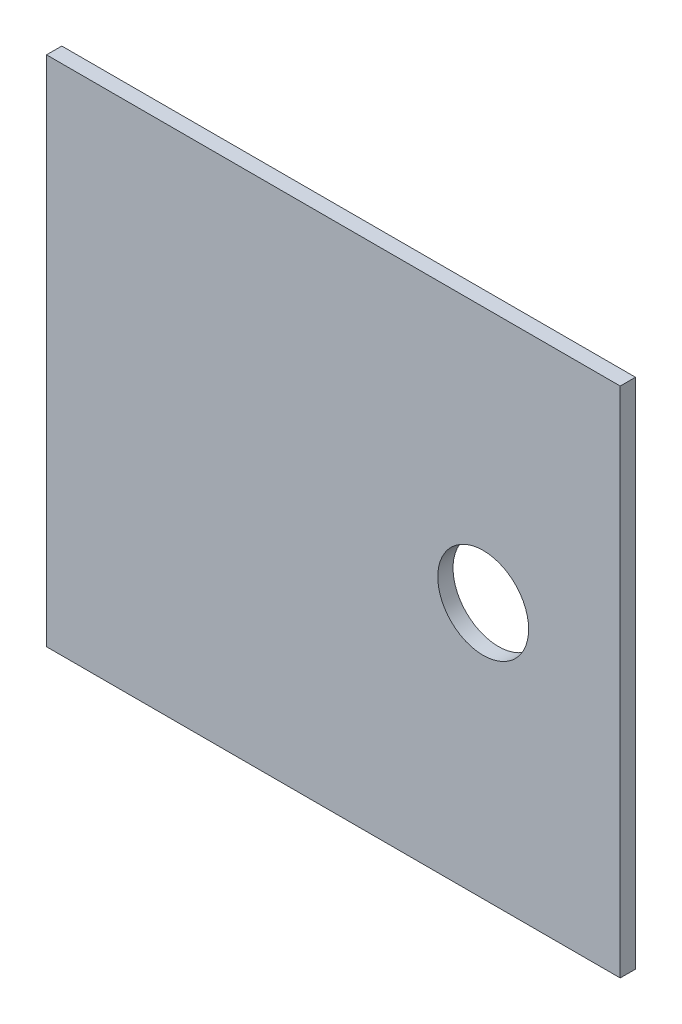
SolidWorks part; units mm, degrees
ref_plane "Alzado" through (0, 0, 0) normal (0, 0, 1) x (1, 0, 0)
ref_plane "Planta" through (0, 0, 0) normal (0, 1, 0) x (1, 0, 0)
ref_plane "Vista lateral" through (0, 0, 0) normal (1, 0, 0) x (0, 0, -1)
sketch "Croquis1" plane through (0, 0, 0) normal (0, 0, 1) x (1, 0, 0)
  line L0 (6.65, 45.25) -> (6.65, 12.25) construction
  line L1 (-64.9, 70.75) -> (29.1, 70.75)
  line L2 (-64.9, 70.75) -> (-64.9, -13.25)
  line L3 (-64.9, -13.25) -> (29.1, -13.25)
  line L4 (29.1, 70.75) -> (29.1, -13.25)
  line L6 (9.3, 12.25) -> (4, 12.25) construction
  circle A0 centre (6.65, 28.75) radius 7.4456
  point P16 (6.65, 12.25)
extrude "Saliente-Extruir1" add sketch "Croquis1" along normal blind 2.5
